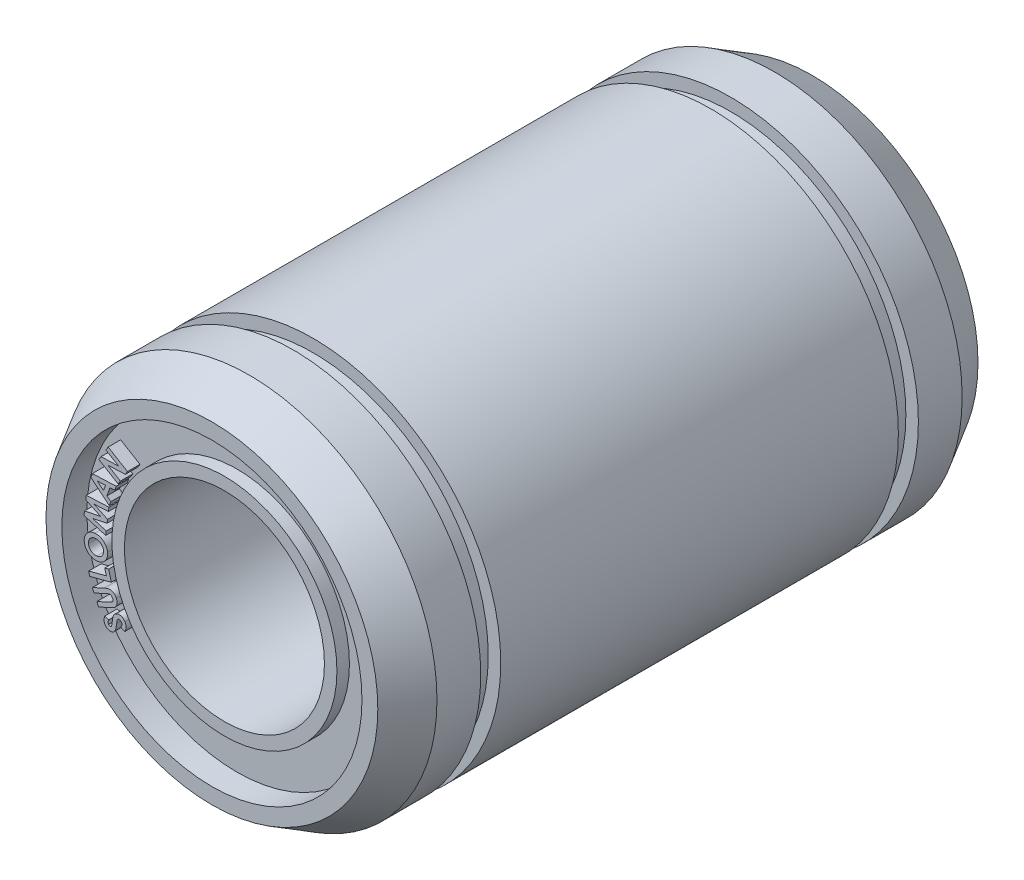
SolidWorks part; units mm, degrees
ref_plane "Front Plane" through (0, 0, 0) normal (0, 0, 1) x (1, 0, 0)
ref_plane "Top Plane" through (0, 0, 0) normal (0, 1, 0) x (1, 0, 0)
ref_plane "Right Plane" through (0, 0, 0) normal (1, 0, 0) x (0, 0, -1)
sketch "Sketch1" plane through (0, 0, 0) normal (0, 0, 1) x (1, 0, 0)
  circle A0 centre (0, 0) radius 7.5
  circle A1 centre (0, 0) radius 6
  dimension "D1" = 15
  dimension "D2" = 12
extrude "Boss-Extrude1" add sketch "Sketch1" along normal mid plane 24
chamfer "Chamfer2" distance 1.5 angle 30 1 edges at (7.5, 0, 12) first distance on face at (7.5, 0, 12)
sketch "Sketch5" plane through (0, 0, 0) normal (0, 0, 1) x (1, 0, 0)
  circle A0 centre (0, 0) radius 6
  circle A1 centre (0, 0) radius 4
  dimension "D1" = 8
extrude "Boss-Extrude2" add sketch "Sketch5" along normal blind 11 and the other way blind 11 separate body
sketch "Sketch6" plane through (0, 0, 11) normal (0, 0, 1) x (1, 0, 0)
  circle A0 centre (0, 0) radius 4
  circle A1 centre (0, 0) radius 4.5
  dimension "D1" = 9
extrude "Boss-Extrude3" add sketch "Sketch6" along normal blind 0.5
mirror "Mirror1" about plane through (0, 0, 0) normal (0, 0, 1) of "Boss-Extrude3"
sketch "Sketch7" plane through (0, 0, 0) normal (1, 0, 0) x (0, 0, -1)
  line L0 (12, 7.5) -> (-10.5, 7.5) construction
  line L1 (-8.75, 7.5) -> (-7.95, 7.5)
  line L2 (-8.75, 7.5) -> (-8.75, 7)
  line L3 (-8.75, 7) -> (-7.95, 7)
  line L4 (-7.95, 7.5) -> (-7.95, 7)
  line L5 (0, 0) -> (5.2365, 0) construction
  line L6 (7.95, 7.5) -> (8.75, 7.5)
  line L7 (7.95, 7.5) -> (7.95, 7)
  line L8 (7.95, 7) -> (8.75, 7)
  line L9 (8.75, 7.5) -> (8.75, 7)
  dimension "D1" = 17.5
  dimension "D2" = 0.8
  dimension "D3" = 0.8
  dimension "D4" = 7.95
  dimension "D5" = 0.5
  dimension "D6" = 0.5
revolve "Cut-Revolve1" cut sketch "Sketch7" angle 360 about L5
sketch "Sketch8" plane through (0, 0, 11) normal (0, 0, 1) x (1, 0, 0)
  circle A0 centre (0, 0) radius 4.7503 construction
  text T0 "SULOMAN" font "Century Gothic" height 0.9
extrude "Boss-Extrude4" add sketch "Sketch8" along normal blind 0.5
ref_plane "Plane1" through (7.5, 0, 0) normal (1, 0, 0) x (0, 0, -1)
chamfer "Chamfer3" distance 1.5 angle 30 1 edges at (7.5, 0, -12) first distance on face at (7.5, 0, -12)
